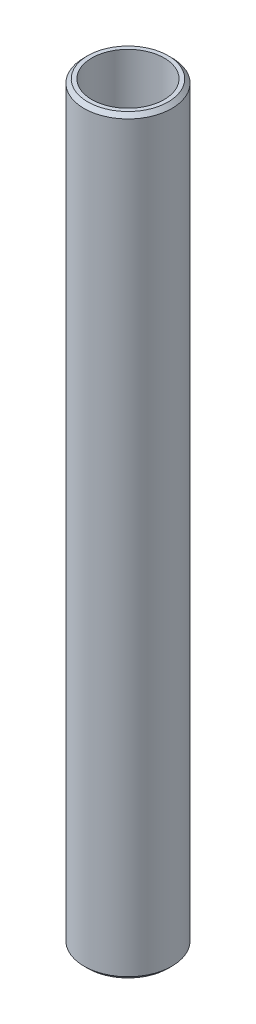
SolidWorks part; units mm, degrees
ref_plane "Front Plane" through (0, 0, 0) normal (0, 0, 1) x (1, 0, 0)
ref_plane "Top Plane" through (0, 0, 0) normal (0, 1, 0) x (1, 0, 0)
ref_plane "Right Plane" through (0, 0, 0) normal (1, 0, 0) x (0, 0, -1)
sketch "Sketch1" plane through (0, 0, 0) normal (0, 1, 0) x (1, 0, 0)
  circle A0 centre (0, 0) radius 35
  dimension "SHAFT_OD" = 70
extrude "Boss-Extrude1" add sketch "Sketch1" along normal blind 598.0669
sketch "Sketch2" plane through (0, 0, 0) normal (0, 1, 0) x (1, 0, 0)
  circle A0 centre (0, 0) radius 28.7923
  dimension "BORE_D" = 57.5846
extrude "Cut-Extrude1" cut sketch "Sketch2" along normal through all
chamfer "Chamfer1" distance 2.996 angle 45 2 edges at (0, 598.0669, 35) (0, 0, 35)
